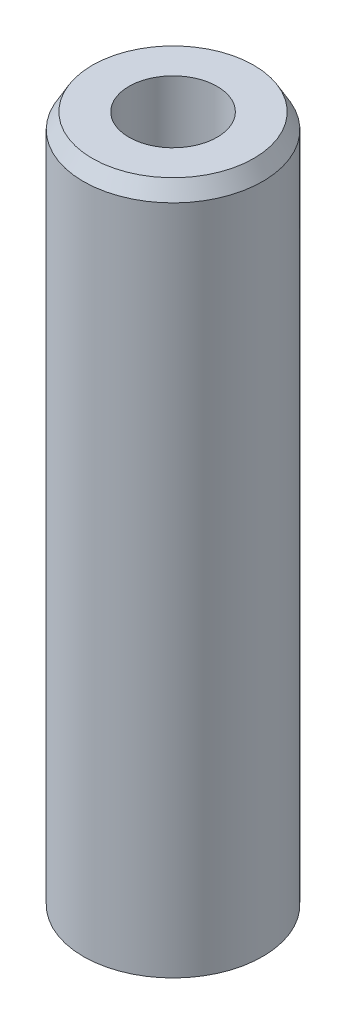
SolidWorks part; units mm, degrees
ref_plane "Front Plane" through (0, 0, 0) normal (0, 0, 1) x (1, 0, 0)
ref_plane "Top Plane" through (0, 0, 0) normal (0, 1, 0) x (1, 0, 0)
ref_plane "Right Plane" through (0, 0, 0) normal (1, 0, 0) x (0, 0, -1)
sketch "Sketch1" plane through (0, 0, 0) normal (0, 1, 0) x (1, 0, 0)
  circle A0 centre (0, 0) radius 7.5
  dimension "SHAFT_OD" = 15
extrude "Boss-Extrude1" add sketch "Sketch1" along normal blind 58.1724
sketch "Sketch2" plane through (0, 0, 0) normal (0, 1, 0) x (1, 0, 0)
  circle A0 centre (0, 0) radius 3.6876
  dimension "BORE_D" = 7.3752
extrude "Cut-Extrude1" cut sketch "Sketch2" along normal through all
chamfer "Chamfer1" distance 1.295 angle 30 2 edges at (0, 58.1724, 7.5) (0, 0, 7.5) first distance on face at (0, 58.1724, 7.5) first distance on face at (0, 0, 3.6876)
